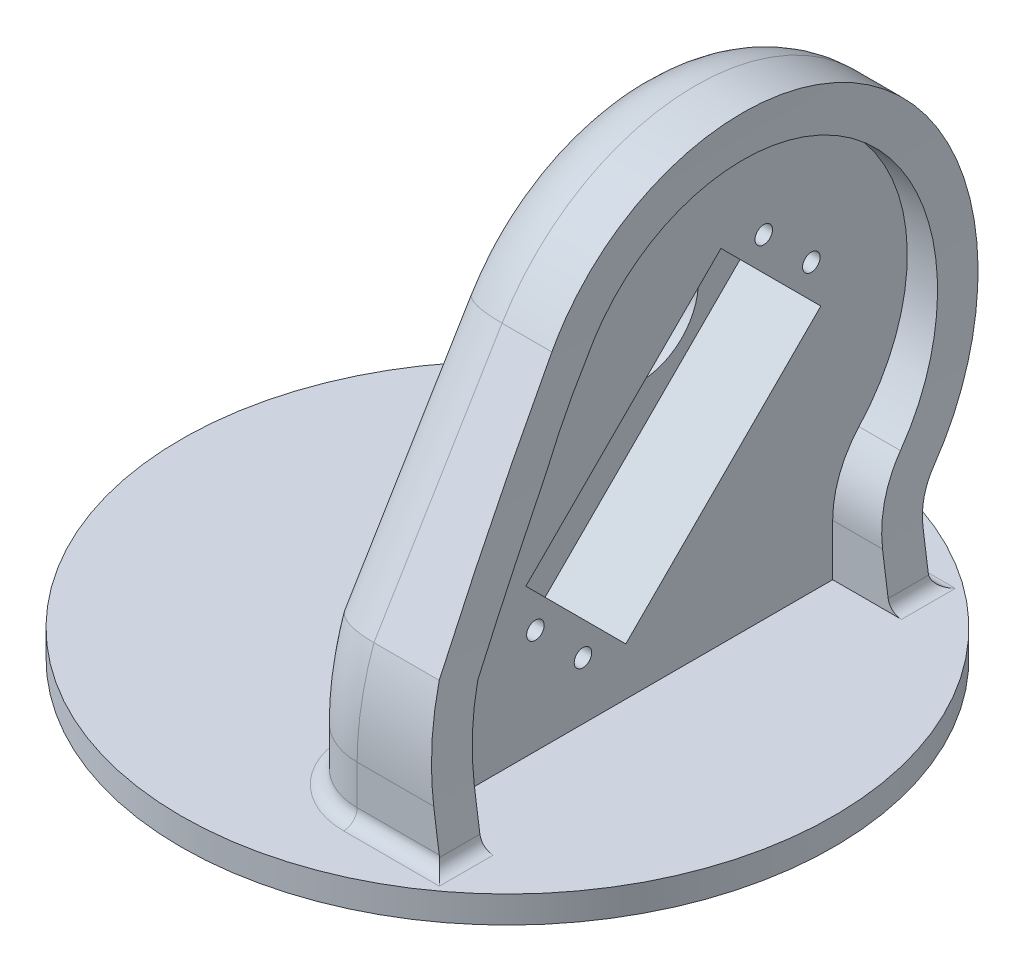
SolidWorks part; units mm, degrees
ref_plane "Front Plane" through (0, 0, 0) normal (0, 0, 1) x (1, 0, 0)
ref_plane "Top Plane" through (0, 0, 0) normal (0, 1, 0) x (1, 0, 0)
ref_plane "Right Plane" through (0, 0, 0) normal (1, 0, 0) x (0, 0, -1)
sketch "Sketch1" plane through (0, 0, 0) normal (0, 1, 0) x (1, 0, 0)
  line L0 (0, 7.25) -> (0, -7.25) construction
  circle A0 centre (0, 0) radius 48.5
  circle A1 centre (0, 7.25) radius 1.5
  circle A2 centre (0, -7.25) radius 1.5
  point P6 (0, 0)
  dimension "D2" = 97
  dimension "D3" = 3
  dimension "D4" = 3
  dimension "D1" = 14.5
extrude "Boss-Extrude2" add sketch "Sketch1" along normal blind 4
sketch "Sketch2" plane through (0, 0, 0) normal (0, -1, 0) x (1, 0, 0)
  circle A0 centre (0, 0) radius 3.75
  dimension "D1" = 7.5
extrude "Cut-Extrude4" cut sketch "Sketch2" against normal blind 1.5
sketch "Sketch3" plane through (0, 0, 0) normal (1, 0, 0) x (0, 0, -1)
  line L0 (-30.34, 4) -> (30.34, 4)
  line L1 (48.5, 4) -> (-48.5, 4) construction
  line L2 (30.34, 4) -> (30.34, 11.64)
  line L3 (-30.34, 4) -> (-30.34, 11.86)
  line L4 (-28.3917, 23.4134) -> (-9.6607, 54.4879)
  arc A0 (30.34, 11.64) -> (34.2527, 21.7431) centre (45.34, 11.64) cw
  arc A1 (34.2527, 21.7431) -> (-9.6607, 54.4879) centre (13.91, 40.28) ccw
  arc A2 (-30.34, 11.86) -> (-28.3917, 23.4134) centre (4.89, 11.86) cw
  circle A3 centre (13.91, 40.28) radius 8.4663
  point P5 (0, 4)
  dimension "D3" = 15
  dimension "D5" = 35.23
  dimension "D6" = 16.9327
  dimension "D1" = 60.68
  dimension "D2" = 7.64
  dimension "D4" = 7.86
  dimension "D7" = 13.91
  dimension "D8" = 40.28
extrude "Boss-Extrude3" add sketch "Sketch3" along normal blind 14 from offset 4
sketch "Sketch4" plane through (0, 0, 0) normal (1, 0, 0) x (0, 0, -1)
  line L0 (-0.41, 11.11) -> (28.5814, 40.1014)
  line L1 (-0.41, 11.11) -> (-15.2592, 25.9592)
  line L2 (28.5814, 40.1014) -> (13.7321, 54.9506)
  line L3 (-15.2592, 25.9592) -> (13.7321, 54.9506)
  line L4 (-30.34, 4) -> (30.34, 4) construction
  line L5 (-0.7636, 40.4549) -> (14.0857, 25.6057) construction
  line L6 (14.0857, 25.6057) -> (6.6611, 33.0303) construction
  line L7 (6.6611, 33.0303) -> (23.6316, 50.0009) construction
  line L8 (20.0961, 53.5364) -> (27.1672, 46.4653)
  circle A0 centre (27.1672, 46.4653) radius 1.3
  circle A1 centre (20.0961, 53.5364) radius 1.3
  circle A2 centre (-6.774, 12.5242) radius 1.3
  circle A3 centre (-13.845, 19.5953) radius 1.3
  point P14 (26.0422, 51.7143)
  point P15 (23.6316, 50.0009)
  dimension "D8" = 2.6
  dimension "D9" = 2.6
  dimension "D1" = 0.41
  dimension "D2" = 11.11
  dimension "D3" = 21
  dimension "D4" = 41
  dimension "D5" = 45
  dimension "D6" = 3.5
  dimension "D7" = 10
extrude "Cut-Extrude5" cut sketch "Sketch4" along normal through all from offset 6 contours L0 L2 L3 L1 | A1 | A0 | A2 | A3
sketch "Sketch5" plane through (18, 0, 0) normal (1, 0, 0) x (0, 0, -1)
  line L4 (30.34, 4) -> (30.34, 11.64)
  line L5 (-9.6607, 54.4879) -> (-28.3917, 23.4134)
  line L6 (-30.34, 11.86) -> (-30.34, 4)
  line L7 (-30.34, 4) -> (30.34, 4)
  line L8 (30.34, 4) -> (30.34, 11.64)
  line L9 (-9.6607, 54.4879) -> (-28.3917, 23.4134)
  line L10 (-30.34, 11.86) -> (-30.34, 4)
  line L11 (-30.34, 4) -> (30.34, 4)
  arc A3 (34.2527, 21.7431) -> (30.34, 11.64) centre (45.34, 11.64) ccw
  arc A4 (34.2527, 21.7431) -> (-9.6607, 54.4879) centre (13.91, 40.28) ccw
  arc A5 (-28.3917, 23.4134) -> (-30.34, 11.86) centre (4.89, 11.86) ccw
  arc A6 (34.2527, 21.7431) -> (30.34, 11.64) centre (45.34, 11.64) ccw
  arc A7 (34.2527, 21.7431) -> (-9.6607, 54.4879) centre (13.91, 40.28) ccw
  arc A8 (-28.3917, 23.4134) -> (-30.34, 11.86) centre (4.89, 11.86) ccw
  dimension "D1" = 0
sketch "Sketch6" plane through (18, 0, 0) normal (1, 0, 0) x (0, 0, -1)
  line L0 (33.34, 4) -> (33.34, 11.64) construction
  line L1 (-12.2301, 56.0366) -> (-31.1196, 24.699) construction
  line L2 (-33.34, 11.86) -> (-33.34, 4) construction
  line L3 (36.34, 4) -> (36.34, 11.64)
  line L4 (30.34, 4) -> (30.34, 11.64)
  line L5 (-9.6607, 54.4879) -> (-28.3917, 23.4134)
  line L6 (-30.34, 11.86) -> (-30.34, 4)
  line L7 (-30.34, 4) -> (30.34, 4)
  line L8 (30.34, 4) -> (30.34, 11.64)
  line L9 (-9.6607, 54.4879) -> (-28.3917, 23.4134)
  line L10 (-30.34, 11.86) -> (-30.34, 4)
  line L11 (-30.34, 4) -> (30.34, 4)
  line L12 (-14.7994, 57.5853) -> (-33.8413, 25.9949)
  line L13 (-36.34, 11.86) -> (-36.34, 4)
  line L14 (-36.34, 4) -> (-27.34, 4)
  line L15 (30.34, 4) -> (36.34, 4)
  arc A0 (36.4702, 19.7225) -> (33.34, 11.64) centre (45.34, 11.64) ccw construction
  arc A1 (36.4702, 19.7225) -> (-12.2301, 56.0366) centre (13.91, 40.28) ccw construction
  arc A2 (-31.1196, 24.699) -> (-33.34, 11.86) centre (4.89, 11.86) ccw construction
  arc A3 (34.2527, 21.7431) -> (30.34, 11.64) centre (45.34, 11.64) ccw
  arc A4 (34.2527, 21.7431) -> (-9.6607, 54.4879) centre (13.91, 40.28) ccw
  arc A5 (-28.3917, 23.4134) -> (-30.34, 11.86) centre (4.89, 11.86) ccw
  arc A6 (34.2527, 21.7431) -> (30.34, 11.64) centre (45.34, 11.64) ccw
  arc A7 (34.2527, 21.7431) -> (-9.6607, 54.4879) centre (13.91, 40.28) ccw
  arc A8 (-28.3917, 23.4134) -> (-30.34, 11.86) centre (4.89, 11.86) ccw
  arc A9 (38.6876, 17.7018) -> (36.34, 11.64) centre (45.34, 11.64) ccw
  arc A10 (38.6876, 17.7018) -> (-14.7994, 57.5853) centre (13.91, 40.28) ccw
  arc A11 (-33.8413, 25.9949) -> (-36.34, 11.86) centre (4.89, 11.86) ccw
  arc A12 (-9.6607, 54.4879) -> (-27.34, 4) centre (72.4419, -2.6012) ccw
  line M20 (30.34, 4) -> (30.34, 11.64)
  arc M21 (30.34, 11.64) -> (34.2527, 21.7431) centre (45.34, 11.64) cw
  arc M22 (34.2527, 21.7431) -> (-9.6607, 54.4879) centre (13.91, 40.28) ccw
  arc M24 (-28.3917, 23.4134) -> (-30.34, 11.86) centre (4.89, 11.86) ccw
  line M25 (-30.34, 11.86) -> (-30.34, 4)
  dimension "D5" = 100
  dimension "D4" = 3
  dimension "D1" = 0
  dimension "D2" = 3
  dimension "D3" = 3
extrude "Boss-Extrude4" add sketch "Sketch6" along normal blind 9 and the other way up to surface (14 mm away) contours A12 L15 L3 A9 A10 L12 A11 L13 L14 L9 M22 M21 M20 M25 M24 region at (18, 5.0904, -33.34) other way up to face at (4, 22.2599, -1.8341)
sketch "Sketch7" plane through (0, 0, 0) normal (0, 0, 1) x (1, 0, 0)
  line L0 (27, 73.8017) -> (21, 73.8017)
  line L1 (48.5, 4) -> (-48.5, 4) construction
  line L2 (26.5, 4) -> (27, 4)
  line L3 (27, 4) -> (27, 73.8017)
  arc A0 (21, 73.8017) -> (26.5, 4) centre (520.9817, 78.08) ccw
  dimension "D3" = 500
  dimension "D1" = 6
  dimension "D2" = 0.5
extrude "Cut-Extrude6" cut sketch "Sketch7" against normal through all both and the other way through all
fillet "Fillet1" radius 10 6 edges at (4, 7.93, 36.34) (4, 7.82, -36.34) (4, 14.8903, -36.9474) (4, 19.037, 35.7105) (4, 41.7901, 24.3204) (4, 67.1531, -33.9484)
fillet "Fillet2" radius 2 7 edges at (26.5, 4, 33.34) (26.5, 4, -33.34) (20.25, 4, -36.34) (6.9289, 4, -33.4111) (20.25, 4, 36.34) (6.9289, 4, 33.4111) (4, 4, 0)
